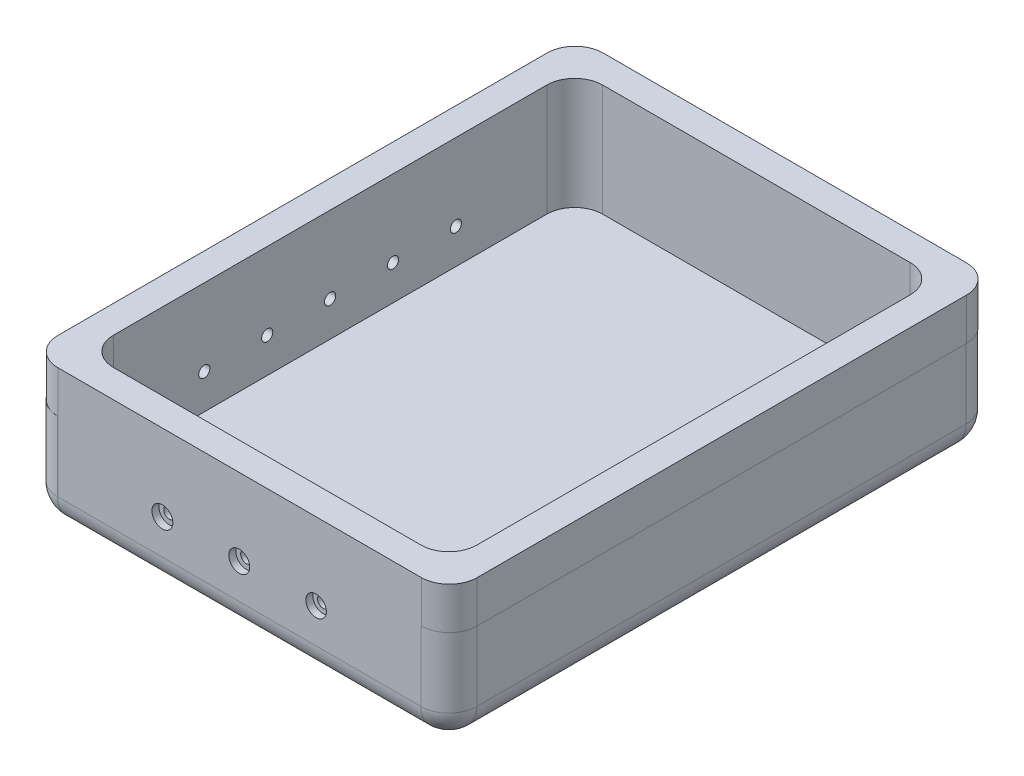
SolidWorks part; units mm, degrees
ref_plane "Front Plane" through (0, 0, 0) normal (0, 0, 1) x (1, 0, 0)
ref_plane "Top Plane" through (0, 0, 0) normal (0, 1, 0) x (1, 0, 0)
ref_plane "Right Plane" through (0, 0, 0) normal (1, 0, 0) x (0, 0, -1)
sketch "Sketch1" plane through (0, 0, 0) normal (0, 1, 0) x (1, 0, 0)
  line L1 (0, 0) -> (66.04, 0)
  line L2 (0, 0) -> (0, 88.9)
  line L3 (0, 88.9) -> (66.04, 88.9)
  line L4 (66.04, 0) -> (66.04, 88.9)
  line L5 (0, 0) -> (-5.08, 0)
  line L6 (0, 0) -> (0, -5.08)
  line L7 (0, -5.08) -> (-5.08, -5.08)
  line L8 (-5.08, 0) -> (-5.08, -5.08)
  line L9 (66.04, 88.9) -> (71.12, 88.9)
  line L10 (66.04, 88.9) -> (66.04, 93.98)
  line L11 (66.04, 93.98) -> (71.12, 93.98)
  line L12 (71.12, 88.9) -> (71.12, 93.98)
  line L13 (-5.08, -5.08) -> (71.12, -5.08)
  line L14 (-5.08, -5.08) -> (-5.08, 93.98)
  line L15 (-5.08, 93.98) -> (71.12, 93.98)
  line L16 (71.12, -5.08) -> (71.12, 93.98)
  dimension "D1" = 88.9
  dimension "D2" = 66.04
  dimension "D3" = 5.08
  dimension "D4" = 5.08
  dimension "D5" = 5.08
  dimension "D6" = 5.08
extrude "Boss-Extrude1" add sketch "Sketch1" against normal blind 12.7 contours L15 L14 L5 L2 L3 L10 | L13 L16 L9 L4 L1 L6 | L5 L8 L7 L6 | L9 L12 L11 L10
sketch "Sketch2" plane through (0, -12.7, 0) normal (0, -1, 0) x (-1, 0, 0)
  line L1 (5.08, 93.98) -> (-71.12, 93.98)
  line L2 (5.08, 93.98) -> (5.08, -5.08)
  line L3 (5.08, -5.08) -> (-71.12, -5.08)
  line L4 (-71.12, 93.98) -> (-71.12, -5.08)
extrude "Boss-Extrude2" add sketch "Sketch2" along normal blind 5.08
fillet "Fillet1" radius 5.08 8 edges at (-5.08, -8.89, 5.08) (33.02, -17.78, 5.08) (71.12, -8.89, 5.08) (71.12, -17.78, -44.45) (71.12, -8.89, -93.98) (33.02, -17.78, -93.98) (-5.08, -8.89, -93.98) (-5.08, -17.78, -44.45)
sketch "Sketch3" plane through (0, 0, 0) normal (0, 1, 0) x (1, 0, 0)
  line L0 (0, 0) -> (66.04, 88.9)
  line L1 (0, 88.9) -> (66.04, 0)
  line L3 (56.1544, 13.3076) -> (9.8856, 13.3076)
  line L4 (56.1544, 13.3076) -> (56.1544, 75.5924)
  line L5 (56.1544, 75.5924) -> (9.8856, 75.5924)
  line L6 (9.8856, 13.3076) -> (9.8856, 75.5924)
  line L7 (56.1544, 13.3076) -> (9.8856, 75.5924) construction
  line L8 (56.1544, 75.5924) -> (9.8856, 13.3076) construction
  circle A0 centre (9.8856, 13.3076) radius 1.143
  circle A1 centre (9.8856, 75.5924) radius 1.143
  circle A2 centre (56.1544, 13.3076) radius 1.143
  circle A3 centre (56.1544, 75.5924) radius 1.143
  point P8 (33.02, 44.45)
extrude "Boss-Extrude3" add sketch "Sketch3" along normal blind 10.922 and the other way up to surface (17.78 mm away) contours L6 A0 L0 | L0 A0 L6 | L3 A0 L0 | L0 A0 L3 | L3 A2 L1 | L1 A2 L3 | L4 A2 L1 | L1 A2 L4 | L5 A3 L0 | L0 A3 L5 | L4 A3 L0 | L0 A3 L4 | L6 A1 L1 | L1 A1 L5 | L5 A1 L1 | L1 A1 L6
sketch "Sketch4" plane through (0, 0, 0) normal (0, 1, 0) x (1, 0, 0)
  circle A0 centre (56.1544, 13.3076) radius 2.032
  circle A1 centre (9.8856, 13.3076) radius 2.032
  circle A2 centre (56.1544, 75.5924) radius 2.032
  circle A3 centre (9.8856, 75.5924) radius 2.032
extrude "Boss-Extrude4" add sketch "Sketch4" against normal up to surface (12.7 mm away) up to face at (9.8856, -12.7, -74.4494)
sketch "Sketch5" plane through (0, 0, 5.08) normal (0, 0, 1) x (1, 0, 0)
  line L0 (0, 0) -> (66.04, -12.7)
  line L1 (66.04, -12.7) -> (0, -12.7)
  line L2 (0, -12.7) -> (66.04, 0)
  line L3 (66.04, 0) -> (0, 0)
  line L5 (7.6171, -8.255) -> (58.4229, -8.255)
  line L6 (7.6171, -8.255) -> (7.6171, -4.445)
  line L7 (7.6171, -4.445) -> (58.4229, -4.445)
  line L8 (58.4229, -8.255) -> (58.4229, -4.445)
  line L9 (7.6171, -8.255) -> (58.4229, -4.445) construction
  line L10 (7.6171, -4.445) -> (58.4229, -8.255) construction
  circle A0 centre (33.02, -6.35) radius 1.905
  circle A1 centre (19.05, -6.35) radius 1.905
  circle A2 centre (46.9899, -6.3885) radius 1.8665
  point P4 (33.02, -6.35)
  dimension "D1" = 13.97
  dimension "D2" = 13.97
sketch "Sketch6" plane through (-5.08, 0, 0) normal (-1, 0, 0) x (0, 0, 1)
  line L0 (-88.9, 0) -> (0, -12.7)
  line L1 (0, -12.7) -> (0, 0)
  line L2 (0, 0) -> (-88.9, -12.7)
  line L3 (-88.9, -12.7) -> (-88.9, 0)
  line L5 (-78.743, -8.255) -> (-10.157, -8.255)
  line L6 (-78.743, -8.255) -> (-78.743, -4.445)
  line L7 (-78.743, -4.445) -> (-10.157, -4.445)
  line L8 (-10.157, -8.255) -> (-10.157, -4.445)
  line L9 (-78.743, -8.255) -> (-10.157, -4.445) construction
  line L10 (-78.743, -4.445) -> (-10.157, -8.255) construction
  circle A0 centre (-44.45, -6.35) radius 1.905
  circle A1 centre (-33.02, -6.35) radius 1.9227
  circle A2 centre (-21.59, -6.35) radius 1.905
  circle A3 centre (-55.88, -6.35) radius 1.905
  circle A4 centre (-67.31, -6.35) radius 1.905
  point P4 (-44.45, -6.35)
  dimension "D1" = 11.43
  dimension "D2" = 11.43
  dimension "D3" = 11.43
  dimension "D4" = 11.43
sketch "Sketch7" plane through (0, 10.922, 0) normal (0, 1, 0) x (1, 0, 0)
  circle A0 centre (56.1544, 75.5924) radius 1.143
  circle A1 centre (9.8856, 75.5924) radius 1.143
  circle A2 centre (56.1544, 13.3076) radius 1.143
  circle A3 centre (9.8856, 13.3076) radius 1.143
extrude "Cut-Extrude4" cut sketch "Sketch7" against normal up to surface (10.922 mm away) up to face at (56.1544, 0, -12.1646)
sketch "Sketch8" plane through (0, 0, 0) normal (0, 1, 0) x (1, 0, 0)
  circle A0 centre (56.1544, 13.3076) radius 2.032
  circle A1 centre (56.1544, 75.5924) radius 2.032
  circle A2 centre (9.8856, 75.5924) radius 2.032
  circle A3 centre (9.8856, 13.3076) radius 2.032
extrude "Cut-Extrude5" cut sketch "Sketch8" against normal up to surface (12.7 mm away) up to face at (9.8856, -12.7, -73.5604)
extrude "Cut-Extrude6" cut sketch "Sketch5" against normal up to surface (5.08 mm away) contours A1 | L2 A0 L0 | L0 A0 L2 | L0 A0 L2 | L2 A0 L0 | A2 up to face at (33.02, -6.35, 0)
sketch "Sketch9" plane through (0, 0, 0) normal (0, 0, -1) x (-1, 0, 0)
  circle A0 centre (-46.9899, -6.3885) radius 1.905
  circle A1 centre (-33.02, -6.35) radius 1.905
  circle A2 centre (-19.05, -6.35) radius 1.905
  circle A3 centre (-46.9899, -6.3885) radius 1.016
  circle A4 centre (-19.05, -6.35) radius 1.016
  circle A5 centre (-33.02, -6.35) radius 1.016
extrude "Boss-Extrude5" add sketch "Sketch9" against normal blind 3.81
extrude "Cut-Extrude7" cut sketch "Sketch6" against normal up to surface (5.08 mm away) contours A2 | L7 A1 L5 | A4 | A3 | L2 A0 L0 | L0 A0 L2 | L0 A0 L2 | L2 A0 L0
sketch "Sketch10" plane through (0, 0, 0) normal (1, 0, 0) x (0, 0, -1)
  circle A0 centre (21.59, -6.35) radius 1.905
  circle A1 centre (33.02, -6.35) radius 2.032
  circle A2 centre (44.45, -6.35) radius 1.905
  circle A3 centre (55.88, -6.35) radius 1.905
  circle A4 centre (67.31, -6.35) radius 1.905
  circle A5 centre (21.59, -6.35) radius 1.016
  circle A6 centre (33.02, -6.35) radius 1.016
  circle A7 centre (44.45, -6.35) radius 1.016
  circle A8 centre (55.88, -6.35) radius 1.016
  circle A9 centre (67.31, -6.35) radius 1.016
extrude "Boss-Extrude8" add sketch "Sketch10" against normal blind 3.81
sketch "Sketch11" plane through (0, 0, 0) normal (0, 1, 0) x (1, 0, 0)
  line L1 (66.04, 88.9) -> (0, 88.9)
  line L2 (66.04, 88.9) -> (66.04, 0)
  line L3 (66.04, 0) -> (0, 0)
  line L4 (0, 88.9) -> (0, 0)
  line L5 (71.1848, 93.98) -> (-5.0152, 93.98)
  line L6 (71.1848, 93.98) -> (71.1848, -5.08)
  line L7 (71.1848, -5.08) -> (-5.0152, -5.08)
  line L8 (-5.0152, 93.98) -> (-5.0152, -5.08)
extrude "Boss-Extrude9" add sketch "Sketch11" along normal blind 7.62
fillet "Fillet5" radius 5.08 8 edges at (71.1848, 3.81, -93.98) (71.1848, 3.81, 5.08) (-5.0152, 3.81, -93.98) (-5.0152, 3.81, 5.08) (66.04, -2.54, 0) (0, -2.54, 0) (66.04, -2.54, -88.9) (0, -2.54, -88.9)
